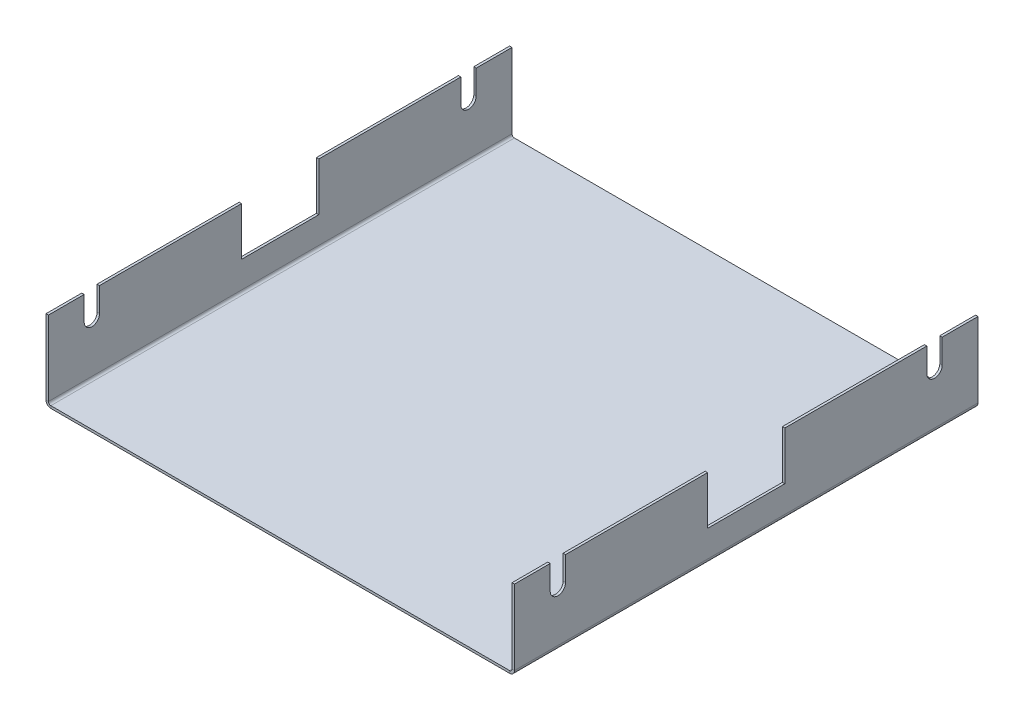
SolidWorks part; units mm, degrees
note: The reader was unsure of these and kept them because the rebuilt part matched: bend radius of "Base-Flange1", "BaseBend1", "BaseBend2".
ref_plane "Front" through (0, 0, 0) normal (0, 0, 1) x (1, 0, 0)
ref_plane "Top" through (0, 0, 0) normal (0, 1, 0) x (1, 0, 0)
ref_plane "Right" through (0, 0, 0) normal (1, 0, 0) x (0, 0, -1)
sketch "Sketch1" plane through (0, 0, 0) normal (0, 0, 1) x (1, 0, 0)
  line L0 (-152.4, 0) -> (152.4, 0)
  line L1 (152.4, 0) -> (152.4, 50.8)
  line L2 (0, -50) -> (0, 50) construction
  line L3 (-152.4, 0) -> (-152.4, 50.8)
  point P8 (0, 0)
  dimension "D1" = 50.8
  dimension "6\"" = 152.4
base flange "Base-Flange1" sketch "Sketch1" end condition mid plane depth 304.8 reverse direction no thickness 1.5875 reverse thickness direction yes bend radius 1.5875
bend "BaseBend1" bend radius 1.5875 bend angle 90 parameters "D5"=1
bend "BaseBend2" bend radius 1.5875 bend angle 90 parameters "D5"=2
sketch "Sketch6" plane through (153.9875, 0, 0) normal (1, 0, 0) x (0, 0, -1)
  line L0 (-152.4, 50.8) -> (152.4, 50.8) construction
  line L1 (-25.4, 50.8) -> (25.4, 50.8)
  line L2 (-25.4, 50.8) -> (-25.4, 19.05)
  line L3 (-25.4, 19.05) -> (25.4, 19.05)
  line L4 (25.4, 50.8) -> (25.4, 19.05)
  line L5 (-152.4, 0) -> (152.4, 0) construction
  point P8 (0, 50.8)
  point P9 (0, 50.8)
  dimension "D1" = 19.05
  dimension "D2" = 50.8
extrude "Cut-Extrude1" cut sketch "Sketch6" against normal through all normal cut yes
hole_wizard "3/8 Clearance Hole1" positions "3DSketch1" profile "Sketch7" hole size "3/8" standard "ANSI Inch" end condition through all
sketch3d "3DSketch1"
  line L0 (153.9875, 50.8, 152.4) -> (153.9875, 1.5875, 152.4) construction
  line L6 (153.9875, 50.8, 152.4) -> (153.9875, 50.8, 25.4) construction
  point P0 (153.9875, 34.925, 123.825)
  point P24 (153.9875, 34.925, -123.825)
  dimension "D1" = 28.575
  dimension "D2" = 15.875
sketch "Sketch7" plane through (153.9875, 34.925, 123.825) normal (0, 1, 0) x (0, 0, -1)
  line L0 (0, 0) -> (0, 307.975)
  line L1 (0, 307.975) -> (5.0419, 307.975)
  line L2 (5.0419, 307.975) -> (5.0419, 0)
  line L5 (5.0419, 0) -> (0, 0)
  line L11 (0, -6.35) -> (0, 107.95) construction
  dimension "Thru Hole Dia." = 10.0838
  dimension "Thru Hole Depth" = 307.975
sketch "Sketch8" plane through (153.9875, 0, 0) normal (1, 0, 0) x (0, 0, -1)
  line L0 (-152.4, 50.8) -> (-25.4, 50.8) construction
  line L1 (-128.8669, 50.8) -> (-118.7831, 50.8)
  line L2 (-128.8669, 50.8) -> (-128.8669, 34.925)
  line L3 (-128.8669, 34.925) -> (-118.7831, 34.925)
  line L4 (-118.7831, 50.8) -> (-118.7831, 34.925)
  line L5 (0, 50) -> (0, -50) construction
  line L6 (128.8669, 34.925) -> (118.7831, 34.925)
  line L7 (118.7831, 50.8) -> (118.7831, 34.925)
  line L8 (128.8669, 50.8) -> (118.7831, 50.8)
  line L9 (128.8669, 50.8) -> (128.8669, 34.925)
  circle A0 centre (-123.825, 34.925) radius 5.0419 construction
extrude "Cut-Extrude2" cut sketch "Sketch8" against normal through all normal cut yes
sketch "Bend-Lines1" [suppressed] plane through (0, 0, 0) normal (0, 1, 0) x (1, 0, 0)
sketch "Bounding-Box1" [suppressed] plane through (0, 0, 0) normal (0, 1, 0) x (1, 0, 0)
sheet metal parameters "Sheet-Metal1" thickness 1.5875 parameters "D1"=1.5875
flat pattern "Flat-Pattern1" [suppressed]
sketch "Bend-Lines2" plane through (0, -1.5875, 0) normal (0, -1, 0) x (-1, 0, 0)
  line L0 (-305.0827, -152.4) -> (-305.0827, 152.4) construction
  line L1 (305.0827, 152.4) -> (305.0827, -152.4) construction
  line L2 (-305.0827, -152.4) -> (-305.0827, 152.4) construction
  line L3 (305.0827, 152.4) -> (305.0827, -152.4) construction
sketch3d "Bounding-Box2" [suppressed]
  line L0 (-660.9655, 304.8, 0) -> (51.3655, 304.8, 0) construction
  line L1 (-660.9655, 0, 0) -> (51.3655, 0, 0) construction
  line L2 (-660.9655, 304.8, 0) -> (-660.9655, 0, 0) construction
  line L3 (51.3655, 304.8, 0) -> (51.3655, 0, 0) construction
bend of the flat pattern "Flatten-<BaseBend1>1"
bend of the flat pattern "Flatten-<BaseBend2>1"
sheet metal parameters "Sheet-Metal2" thickness 1.5875 parameters "D1"=1.5875
flat pattern "Flat-Pattern1"
sketch "Bend-Lines2" plane through (0, -1.5875, 0) normal (0, -1, 0) x (-1, 0, 0)
  line L0 (-305.0827, -152.4) -> (-305.0827, 152.4) construction
  line L1 (305.0827, 152.4) -> (305.0827, -152.4) construction
  line L2 (-305.0827, -152.4) -> (-305.0827, 152.4) construction
  line L3 (305.0827, 152.4) -> (305.0827, -152.4) construction
sketch3d "Bounding-Box2" [suppressed]
  line L0 (-660.9655, 304.8, 0) -> (51.3655, 304.8, 0) construction
  line L1 (-660.9655, 0, 0) -> (51.3655, 0, 0) construction
  line L2 (-660.9655, 304.8, 0) -> (-660.9655, 0, 0) construction
  line L3 (51.3655, 304.8, 0) -> (51.3655, 0, 0) construction
bend of the flat pattern "Flatten-<BaseBend1>1"
bend of the flat pattern "Flatten-<BaseBend2>1"
sheet metal parameters "Sheet-Metal3" thickness 1.5875 parameters "D1"=1.5875
flat pattern "Flat-Pattern1"
sketch "Bend-Lines2" plane through (0, -1.5875, 0) normal (0, -1, 0) x (-1, 0, 0)
  line L0 (-152.6827, -152.4) -> (-152.6827, 152.4) construction
  line L1 (152.6827, 152.4) -> (152.6827, -152.4) construction
  line L2 (-152.6827, -152.4) -> (-152.6827, 152.4) construction
  line L3 (152.6827, 152.4) -> (152.6827, -152.4) construction
sketch3d "Bounding-Box2" [suppressed]
  line L0 (-356.1655, 304.8, 0) -> (51.3655, 304.8, 0) construction
  line L1 (-356.1655, 0, 0) -> (51.3655, 0, 0) construction
  line L2 (-356.1655, 304.8, 0) -> (-356.1655, 0, 0) construction
  line L3 (51.3655, 304.8, 0) -> (51.3655, 0, 0) construction
bend of the flat pattern "Flatten-<BaseBend1>1"
bend of the flat pattern "Flatten-<BaseBend2>1"
sheet metal parameters "Sheet-Metal4" thickness 1.5875 parameters "D1"=1.5875
flat pattern "Flat-Pattern1"
sketch "Bend-Lines2" plane through (0, -1.5875, 0) normal (0, -1, 0) x (-1, 0, 0)
  line L0 (-152.6827, -152.4) -> (-152.6827, 152.4) construction
  line L1 (152.6827, 152.4) -> (152.6827, -152.4) construction
  line L2 (-152.6827, -152.4) -> (-152.6827, 152.4) construction
  line L3 (152.6827, 152.4) -> (152.6827, -152.4) construction
sketch3d "Bounding-Box2" [suppressed]
  line L0 (-356.1655, 304.8, 0) -> (51.3655, 304.8, 0) construction
  line L1 (-356.1655, 0, 0) -> (51.3655, 0, 0) construction
  line L2 (-356.1655, 304.8, 0) -> (-356.1655, 0, 0) construction
  line L3 (51.3655, 304.8, 0) -> (51.3655, 0, 0) construction
bend of the flat pattern "Flatten-<BaseBend1>1"
bend of the flat pattern "Flatten-<BaseBend2>1"
